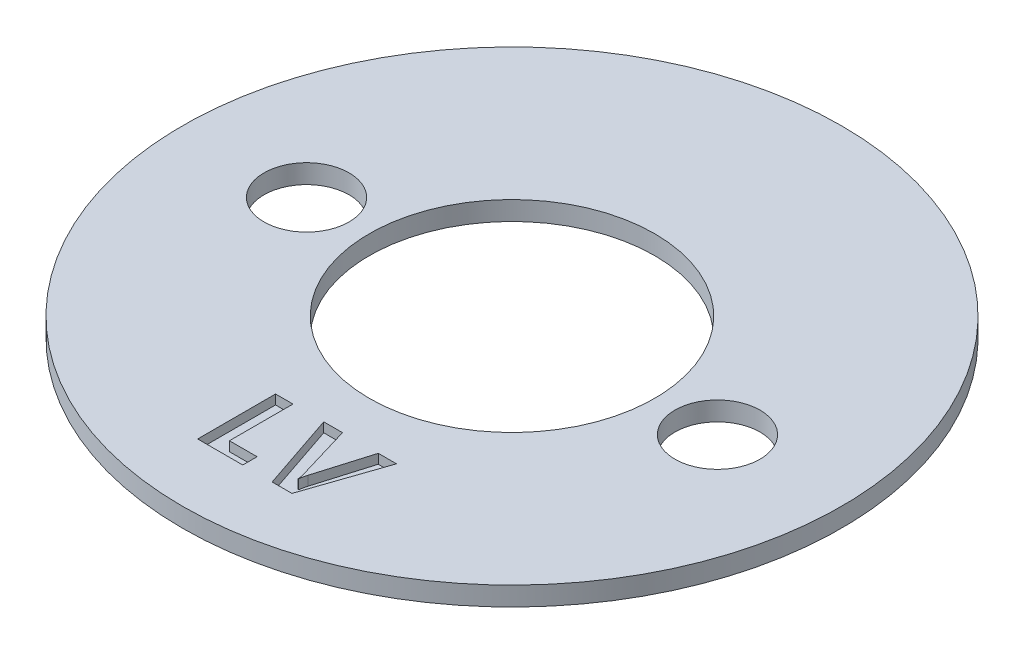
SolidWorks part; units mm, degrees
material "ABS"
ref_plane "Front Plane" through (0, 0, 0) normal (0, 0, 1) x (1, 0, 0)
ref_plane "Top Plane" through (0, 0, 0) normal (0, 1, 0) x (1, 0, 0)
ref_plane "Right Plane" through (0, 0, 0) normal (1, 0, 0) x (0, 0, -1)
sketch "Sketch1" plane through (0, 0, 0) normal (0, 1, 0) x (1, 0, 0)
  circle A0 centre (0, 0) radius 27.5
  dimension "D1" = 55
extrude "Boss-Extrude1" add sketch "Sketch1" along normal blind 1.5875
sketch "Sketch4" plane through (0, 0, 0) normal (0, -1, 0) x (1, 0, 0)
  line L0 (-17.145, 0) -> (17.145, 0) construction
  circle A4 centre (-17.145, 0) radius 3.55
  circle A5 centre (0, 0) radius 11.9062
  circle A6 centre (17.145, 0) radius 3.55
  dimension "D1" = 34.29
  dimension "D2" = 23.8125
  dimension "D3" = 7.1
extrude "Cut-Extrude2" cut sketch "Sketch4" against normal through all
sketch "Sketch2" plane through (0, 1.5875, 0) normal (0, 1, 0) x (1, 0, 0)
  line L0 (-5, -22) -> (5, -22) construction
  line L1 (0, 0) -> (0, -22) construction
  text T0 "LV" font "Nirmala UI" height 6.5
  dimension "D1" = 10
  dimension "D2" = 22
extrude "Cut-Extrude1" cut sketch "Sketch2" against normal offset from surface (0.7938 mm away) 0.7937 up to face at (-17.145, 0, -3.55)
